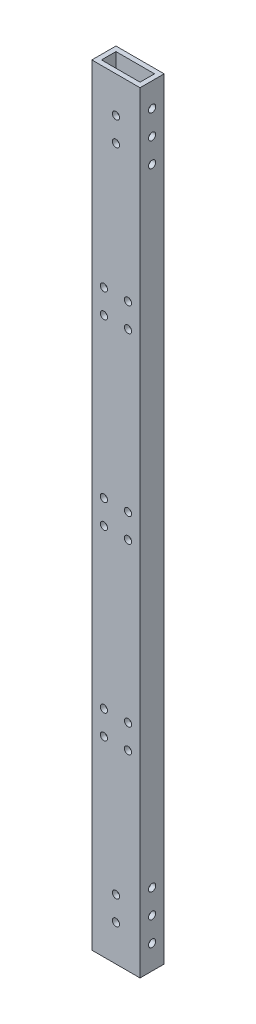
SolidWorks part; units mm, degrees
ref_plane "前视基准面" through (0, 0, 0) normal (0, 0, 1) x (1, 0, 0)
ref_plane "上视基准面" through (0, 0, 0) normal (0, 1, 0) x (1, 0, 0)
ref_plane "右视基准面" through (0, 0, 0) normal (1, 0, 0) x (0, 0, -1)
sketch "草图1" plane through (0, 0, 0) normal (0, 1, 0) x (1, 0, 0)
  line L1 (-10, 5) -> (10, 5)
  line L2 (-10, 5) -> (-10, -5)
  line L3 (-10, -5) -> (10, -5)
  line L4 (10, 5) -> (10, -5)
  line L5 (-10, 5) -> (10, -5) construction
  line L6 (-10, -5) -> (10, 5) construction
  line L7 (-8, 3) -> (8, 3)
  line L8 (-8, 3) -> (-8, -3)
  line L9 (-8, -3) -> (8, -3)
  line L10 (8, 3) -> (8, -3)
  line L11 (-8, 3) -> (8, -3) construction
  line L12 (-8, -3) -> (8, 3) construction
  point P0 (0, 0)
  point P6 (0, 0)
  dimension "D1" = 10
  dimension "D2" = 20
  dimension "D3" = 2
  dimension "D4" = 2
extrude "凸台-拉伸1" add sketch "草图1" along normal mid plane 320
sketch "草图3" plane through (10, 0, 0) normal (1, 0, 0) x (0, 0, -1)
  line L0 (0, 130) -> (0, 150) construction
  line L1 (-5, 160) -> (5, 160) construction
  line L2 (0, 0) -> (20.3275, 0) construction
  circle A0 centre (0, 150) radius 1.5
  circle A1 centre (0, 140) radius 1.5
  circle A2 centre (0, 130) radius 1.5
  circle A3 centre (0, -130) radius 1.5
  circle A4 centre (0, -140) radius 1.5
  circle A5 centre (0, -150) radius 1.5
  dimension "D4" = 3
  dimension "D1" = 10
  dimension "D2" = 10
  dimension "D3" = 10
extrude "切除-拉伸1" cut sketch "草图3" against normal through all
sketch "草图4" plane through (0, 0, -5) normal (0, 0, -1) x (-1, 0, 0)
  line L0 (97, 85.7) -> (-57, 85.7) construction
  line L1 (-5, 70.7) -> (5, 70.7) construction
  line L2 (-5, 70.7) -> (-5, 80.7) construction
  line L3 (-5, 80.7) -> (5, 80.7) construction
  line L4 (5, 70.7) -> (5, 80.7) construction
  line L5 (-5, 70.7) -> (5, 80.7) construction
  line L6 (-5, 80.7) -> (5, 70.7) construction
  line L7 (97, 65.7) -> (-57, 65.7) construction
  line L8 (-10, 160) -> (-10, -160) construction
  line L9 (0, 0) -> (-33.2787, 0) construction
  line L10 (10, 160) -> (-10, 160) construction
  line L11 (0, 145) -> (0, 135) construction
  line L12 (10, 160) -> (10, -160) construction
  circle A0 centre (-5, 70.7) radius 1.5
  circle A1 centre (-5, 80.7) radius 1.5
  circle A2 centre (5, 70.7) radius 1.5
  circle A3 centre (5, 80.7) radius 1.5
  circle A4 centre (5, -70.7) radius 1.5
  circle A5 centre (5, -80.7) radius 1.5
  circle A6 centre (-5, -80.7) radius 1.5
  circle A7 centre (-5, -70.7) radius 1.5
  circle A8 centre (0, 145) radius 1.5
  circle A9 centre (0, 135) radius 1.5
  circle A10 centre (0, -145) radius 1.5
  circle A11 centre (0, -135) radius 1.5
  point P8 (0, 75.7)
  dimension "D4" = 3
  dimension "D1" = 5
  dimension "D2" = 5
  dimension "D3" = 5
  dimension "D5" = 15
  dimension "D6" = 10
  dimension "D7" = 10
extrude "切除-拉伸2" cut sketch "草图4" against normal through all
sketch "草图5" plane through (0, 0, -5) normal (0, 0, -1) x (-1, 0, 0)
  circle A0 centre (5, -5) radius 1.5
  circle A1 centre (-5, -5) radius 1.5
  circle A2 centre (-5, 5) radius 1.5
  circle A3 centre (5, 5) radius 1.5
  circle A4 centre (45, 5) radius 1.5
  circle A5 centre (45, -5) radius 1.5
  circle A6 centre (35, 5) radius 1.5
  circle A7 centre (35, -5) radius 1.5
  circle A8 centre (35, 5) radius 1.5 construction
  point P21 (27.3956, 7.4793)
  point P24 (10.7555, -7.3209)
  point P25 (5.0214, -5)
  point P26 (5, 5)
  point P28 (5, -5)
  dimension "D1" = 3
extrude "切除-拉伸3" cut sketch "草图5" against normal through all
